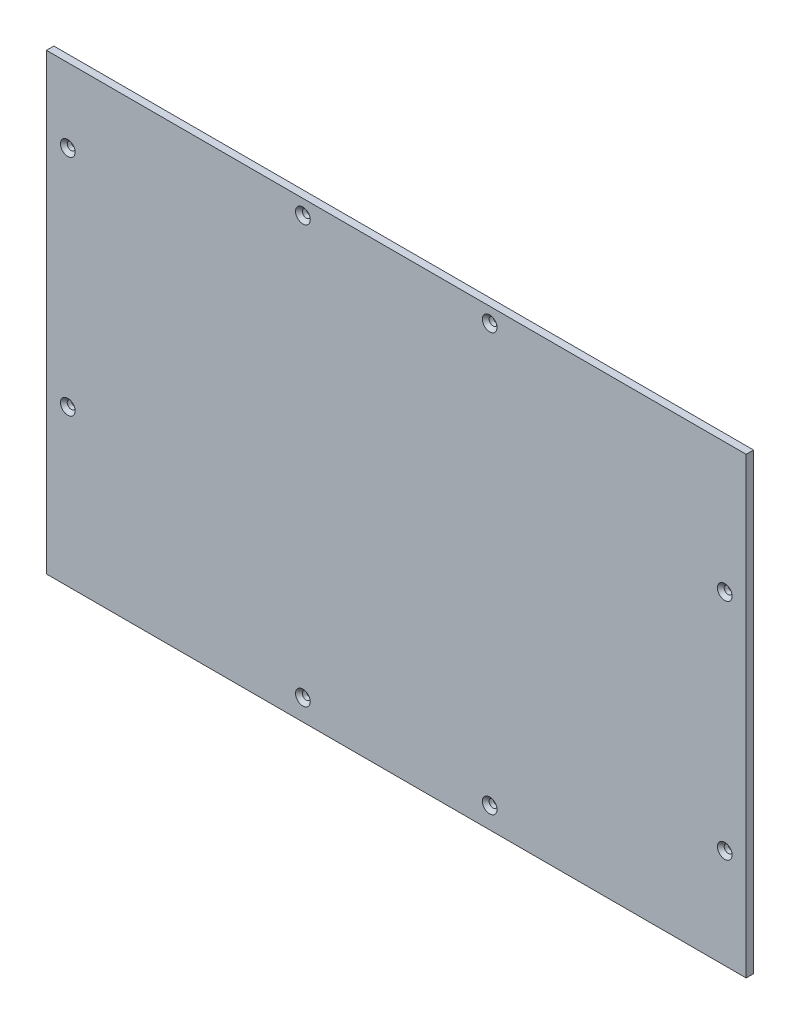
SolidWorks part; units mm, degrees
material "ABS"
ref_plane "X-Y Datum" through (0, 0, 0) normal (0, 0, 1) x (1, 0, 0)
ref_plane "X-Z Datum" through (0, 0, 0) normal (0, 1, 0) x (1, 0, 0)
ref_plane "Y-Z Datum" through (0, 0, 0) normal (1, 0, 0) x (0, 0, -1)
sketch "Sketch1" plane through (0, 0, 0) normal (0, 0, 1) x (1, 0, 0)
  line L0 (-149.85, 97.125) -> (-149.85, -97.125)
  line L1 (-149.85, 97.125) -> (149.85, 97.125)
  line L2 (-149.85, 97.125) -> (-149.85, -97.125)
  line L3 (-149.85, -97.125) -> (149.85, -97.125)
  line L4 (149.85, 97.125) -> (149.85, -97.125)
  line L5 (-149.85, 97.125) -> (149.85, -97.125) construction
  line L6 (-149.85, -97.125) -> (149.85, 97.125) construction
  line L7 (-149.85, -97.125) -> (149.85, -97.125)
  line L8 (149.85, 97.125) -> (149.85, -97.125)
  line L9 (-149.85, 97.125) -> (149.85, 97.125)
  circle A0 centre (-139.075, -86.35) radius 10.775
  circle A1 centre (-115.075, -86.35) radius 10.775 construction
  circle A2 centre (-127.075, -63.35) radius 10.775
  point P0 (0, 0)
  dimension "D1" = 21.55
  dimension "D2" = 24
  dimension "D3" = 23
  dimension "D4" = 12
  dimension "D5" = 194.25
  dimension "D6" = 299.7
  dimension "D7" = 0
extrude "Boss-Extrude1" add sketch "Sketch1" along normal blind 3.175 contours A0 L3 L4 L1 L2 A2 | A2 | A0 | A0 L2 L3 | L9 L0 L7 L8 L1 L4 L3 L2 region at (1.7533, 0.9913, 0) region at (-147.4432, -94.7182, 0) region at (-139.075, -86.35, 0) region at (-127.075, -63.35, 0)
sketch "Sketch2" plane through (0, 0, 3.175) normal (0, 0, 1) x (1, 0, 0)
  point P0 (140.6875, -54.525)
  point P1 (140.6875, 41.475)
  point P3 (40, 90.775)
  point P5 (-40, 90.775)
  point P7 (-140.6875, 65.475)
  point P9 (-140.6875, -30.525)
  point P11 (-40, -88.0307)
  point P13 (40, -88.0307)
hole_wizard "CSK for M3 Flat Head Machine Screw1" positions "Sketch3" profile "Sketch4" countersink size "M3" standard "ANSI Metric" end condition through all
sketch "Sketch3" plane through (0, 0, 3.175) normal (0, 0, 1) x (1, 0, 0)
  point P0 (40, 90.775)
  point P3 (140.6875, 41.475)
  point P6 (140.6875, -54.525)
  point P9 (-40, -88.0307)
  point P12 (40, -88.0307)
  point P15 (-140.6875, -30.525)
  point P18 (-140.6875, 65.475)
  point P21 (-40, 90.775)
sketch "Sketch4" plane through (40, 90.775, 3.175) normal (1, 0, 0) x (0, -1, 0)
  line L0 (0, 0) -> (0, 3.175)
  line L1 (0, 3.175) -> (1.7, 3.175)
  line L2 (1.7, 3.175) -> (1.7, 1.45)
  line L3 (1.7, 1.45) -> (3.15, 0)
  line L5 (3.15, 0) -> (0, 0)
  line L6 (-1.7, 1.45) -> (-3.15, 0) construction
  line L11 (0, -6.35) -> (0, 107.95) construction
  dimension "Thru Hole Dia." = 3.4
  dimension "Thru Hole Depth" = 3.175
  dimension "Near C'Sink Dia." = 6.3
  dimension "Near C'Sink Angle" = 90
